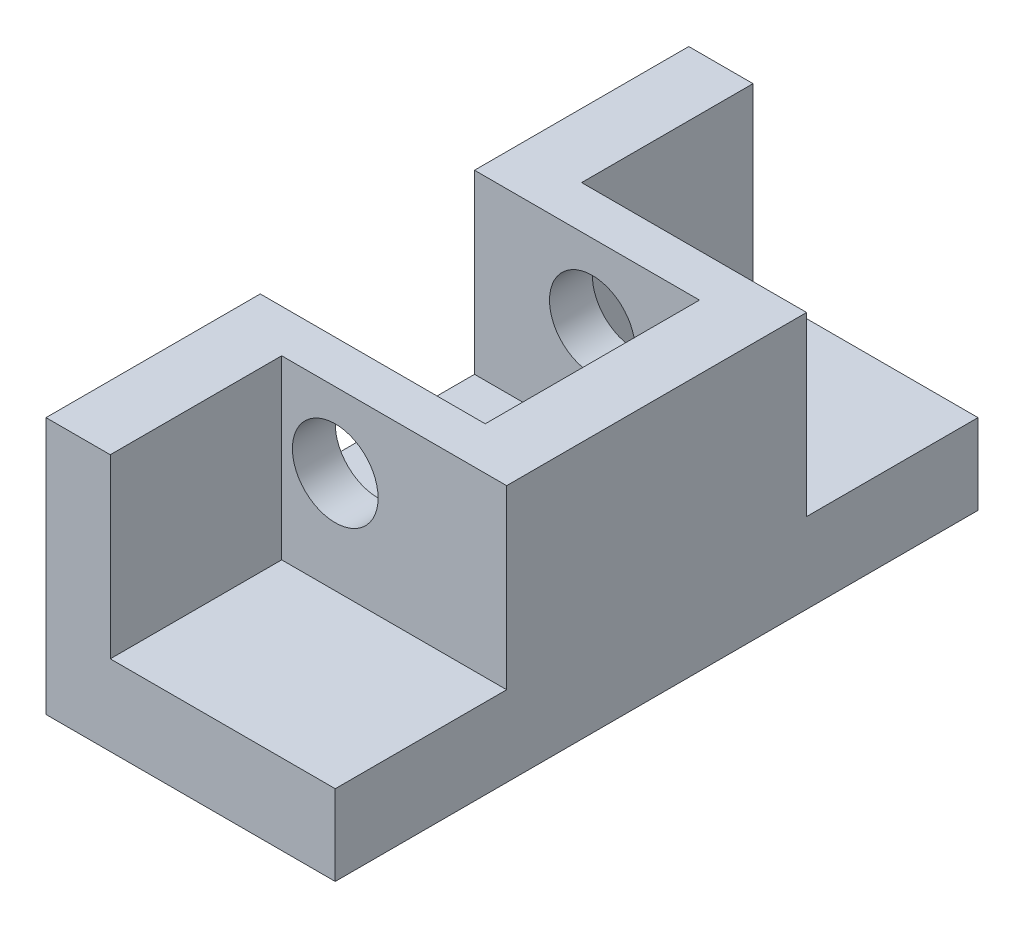
SolidWorks part; units mm, degrees
ref_plane "Front Plane" through (0, 0, 0) normal (0, 0, 1) x (1, 0, 0)
ref_plane "Top Plane" through (0, 0, 0) normal (0, 1, 0) x (1, 0, 0)
ref_plane "Right Plane" through (0, 0, 0) normal (1, 0, 0) x (0, 0, -1)
sketch "Sketch2" plane through (0, 0, 0) normal (0, 1, 0) x (1, 0, 0)
  line L1 (13.5, -30) -> (-13.5, -30)
  line L2 (13.5, -30) -> (13.5, 30)
  line L3 (13.5, 30) -> (-13.5, 30)
  line L4 (-13.5, -30) -> (-13.5, 30)
  line L5 (13.5, -30) -> (-13.5, 30) construction
  line L6 (13.5, 30) -> (-13.5, -30) construction
  point P0 (0, 0)
  dimension "D1" = 60
  dimension "D2" = 27
extrude "Boss-Extrude1" add sketch "Sketch2" along normal blind 7.5
sketch "Sketch3" plane through (0, 7.5, 0) normal (0, 1, 0) x (1, 0, 0)
  line L0 (-13.5, -30) -> (-7.5, -30)
  line L1 (-13.5, -30) -> (13.5, -30) construction
  line L2 (-7.5, -30) -> (-7.5, -14)
  line L4 (-13.5, 30) -> (-13.5, 10)
  line L7 (-13.5, 30) -> (-13.5, -30) construction
  line L10 (-13.5, 10) -> (7.5, 10)
  line L12 (13.5, -14) -> (13.5, 14)
  line L13 (13.5, 14) -> (-7.5, 14)
  line L14 (-7.5, 14) -> (-7.5, 30)
  line L15 (13.5, 30) -> (-13.5, 30) construction
  line L16 (-7.5, 30) -> (-13.5, 30)
  line L18 (13.5, -14) -> (-7.5, -14)
  line L19 (7.5, 10) -> (7.5, -10)
  line L20 (7.5, -10) -> (-13.5, -10)
  line L21 (-13.5, -10) -> (-13.5, -30)
  line L23 (13.5, -30) -> (13.5, 30) construction
  point P5 (10.81, 14.0618)
  point P18 (13.5, 0)
  dimension "D1" = 20
  dimension "D2" = 6
  dimension "D3" = 4
  dimension "D4" = 6
  dimension "D5" = 4
  dimension "D6" = 6
extrude "Boss-Extrude2" add sketch "Sketch3" along normal blind 16.5
sketch "Sketch4" plane through (0, 0, 14) normal (0, 0, 1) x (1, 0, 0)
  line L0 (-7.5, 24) -> (13.5, 24) construction
  line L1 (-7.5, 24) -> (-7.5, 7.5) construction
  circle A0 centre (-2.5, 17) radius 4
  dimension "D1" = 8
  dimension "D2" = 7
  dimension "D3" = 5
extrude "Cut-Extrude1" cut sketch "Sketch4" against normal through all
